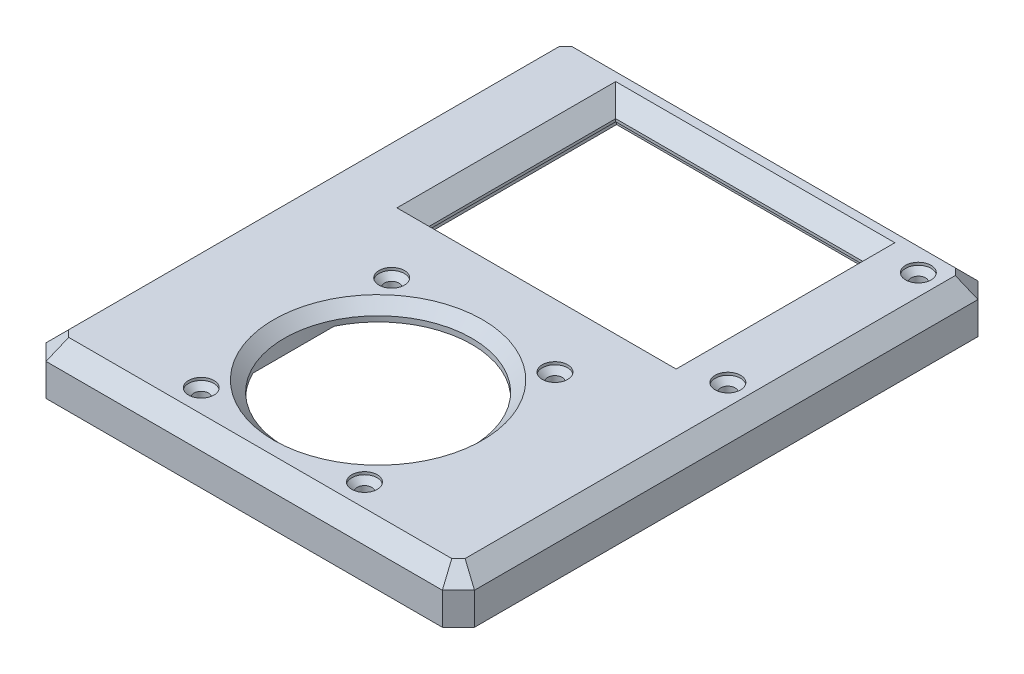
SolidWorks part; units mm, degrees
ref_plane "Front Plane" through (0, 0, 0) normal (0, 0, 1) x (1, 0, 0)
ref_plane "Top Plane" through (0, 0, 0) normal (0, 1, 0) x (1, 0, 0)
ref_plane "Right Plane" through (0, 0, 0) normal (1, 0, 0) x (0, 0, -1)
sketch "Sketch1" plane through (0, 0, 0) normal (0, 1, 0) x (1, 0, 0)
  line L1 (40, 50) -> (-40, 50)
  line L2 (40, 50) -> (40, -50)
  line L3 (40, -50) -> (-40, -50)
  line L4 (-40, 50) -> (-40, -50)
  line L5 (40, 50) -> (-40, -50) construction
  line L6 (40, -50) -> (-40, 50) construction
  point P0 (0, 0)
  dimension "D1" = 80
  dimension "D2" = 100
extrude "Main Base" add sketch "Sketch1" along normal blind 9
sketch "Sketch2" plane through (0, 0, 0) normal (0, -1, 0) x (1, 0, 0)
  circle A0 centre (0, 25) radius 17.5
  dimension "D1" = 35
  dimension "D2" = 25
extrude "ANO Main Wheel Hole" cut sketch "Sketch2" against normal through all both and the other way through all
chamfer "ANO Main Wheel Hole Chamfer" distance 2 angle 45 1 edges at (0, 9, 7.5)
sketch "Sketch3" plane through (0, 0, 0) normal (0, -1, 0) x (1, 0, 0)
  line L0 (15.24, 7.22) -> (-15.24, 42.78) construction
  circle A0 centre (-15.24, 42.78) radius 1.35
  circle A1 centre (15.24, 42.78) radius 1.35
  circle A2 centre (15.24, 7.22) radius 1.35
  circle A3 centre (-15.24, 7.22) radius 1.35
  circle A4 centre (0, 25) radius 17.5 construction
  circle A5 centre (0, 25) radius 17.5 construction
  point P16 (0, 25)
  dimension "D1" = 2.7
  dimension "D2" = 30.48
  dimension "D3" = 35.56
extrude "ANO Mount Holes Cut" cut sketch "Sketch3" against normal through all and the other way through all
sketch "ANO Board Dimensions" plane through (0, 0, 0) normal (0, -1, 0) x (1, 0, 0)
  line L0 (-17.78, 7.22) -> (-17.78, 42.78)
  line L5 (-15.24, 45.32) -> (15.24, 45.32)
  line L6 (17.78, 42.78) -> (17.78, 7.22)
  line L7 (15.24, 4.68) -> (-15.24, 4.68)
  circle A0 centre (-15.24, 42.78) radius 2.54
  circle A1 centre (-15.24, 7.22) radius 2.54
  circle A2 centre (15.24, 7.22) radius 2.54
  circle A3 centre (15.24, 42.78) radius 2.54
  arc A5 (-17.78, 7.22) -> (-15.24, 4.68) centre (-15.24, 7.22) ccw
  arc A6 (17.78, 7.22) -> (15.24, 4.68) centre (15.24, 7.22) cw
  arc A7 (15.24, 45.32) -> (17.78, 42.78) centre (15.24, 42.78) cw
  arc A8 (-17.78, 42.78) -> (-15.24, 45.32) centre (-15.24, 42.78) cw
  dimension "D2" = 35.56
  dimension "D3" = 40.64
sketch "Sketch6" plane through (0, 0, 0) normal (0, -1, 0) x (1, 0, 0)
  line L0 (-17.78, 25) -> (-17.78, 37.7)
  line L1 (-17.78, 7.22) -> (-17.78, 42.78) construction
  line L2 (-15.24, 45.32) -> (15.24, 45.32) construction
  line L3 (-10.16, 45.32) -> (10.16, 45.32)
  line L4 (0, 25) -> (-17.78, 25) construction
  line L5 (0, 25) -> (0, 45.32) construction
  line L12 (17.78, 25) -> (17.78, 37.7)
  line L13 (-17.78, 25) -> (-17.78, 12.3)
  line L15 (-10.16, 4.68) -> (10.16, 4.68)
  line L16 (17.78, 12.3) -> (17.78, 25)
  arc A0 (-17.78, 37.7) -> (-15.24, 40.24) centre (-15.24, 37.7) cw
  circle A1 centre (-15.24, 42.78) radius 2.54 construction
  arc A2 (-15.24, 40.24) -> (-12.7, 42.78) centre (-15.24, 42.78) ccw
  arc A3 (-12.7, 42.78) -> (-10.16, 45.32) centre (-10.16, 42.78) cw
  arc A13 (17.78, 37.7) -> (15.24, 40.24) centre (15.24, 37.7) ccw
  arc A14 (15.24, 40.24) -> (12.7, 42.78) centre (15.24, 42.78) cw
  arc A15 (12.7, 42.78) -> (10.16, 45.32) centre (10.16, 42.78) ccw
  arc A16 (-17.78, 12.3) -> (-15.24, 9.76) centre (-15.24, 12.3) ccw
  arc A17 (-15.24, 9.76) -> (-12.7, 7.22) centre (-15.24, 7.22) cw
  arc A18 (-12.7, 7.22) -> (-10.16, 4.68) centre (-10.16, 7.22) ccw
  arc A19 (10.16, 4.68) -> (12.7, 7.22) centre (10.16, 7.22) ccw
  arc A20 (12.7, 7.22) -> (15.24, 9.76) centre (15.24, 7.22) cw
  arc A21 (15.24, 9.76) -> (17.78, 12.3) centre (15.24, 12.3) ccw
  circle A22 centre (-15.24, 7.22) radius 1.35 construction
  circle A23 centre (15.24, 7.22) radius 1.35 construction
  point P14 (0, 25)
  point P44 (0, 0)
  point P45 (-12.7, 6.7753)
  point P46 (-10.1696, 7.0635)
  point P47 (16.3063, 9.5253)
  point P48 (0, 25)
extrude "ANO Board Offset Cut" cut sketch "Sketch6" against normal offset from surface (6 mm away) 3 up to face at (-15.24, 9, 5.87)
sketch "Sketch12" plane through (0, 0, 0) normal (0, -1, 0) x (1, 0, 0)
  line L0 (15.24, 4.68) -> (-15.24, 4.68) construction
  line L5 (17.78, 42.78) -> (17.78, 7.22) construction
  line L6 (-15.24, 45.32) -> (15.24, 45.32) construction
  line L7 (-17.78, 7.22) -> (-17.78, 42.78) construction
  line L20 (15.24, 4.68) -> (-15.24, 4.68) construction
  line L21 (17.78, 42.78) -> (17.78, 7.22) construction
  line L22 (-15.24, 45.32) -> (15.24, 45.32) construction
  line L23 (-17.78, 7.22) -> (-17.78, 42.78) construction
  line L24 (18.28, 42.78) -> (18.28, 7.22)
  line L25 (-15.24, 45.82) -> (15.24, 45.82)
  line L26 (-18.28, 7.22) -> (-18.28, 42.78)
  line L27 (15.24, 4.18) -> (-15.24, 4.18)
  arc A3 (-17.78, 42.78) -> (-15.24, 45.32) centre (-15.24, 42.78) cw construction
  arc A4 (17.78, 42.78) -> (15.24, 45.32) centre (15.24, 42.78) ccw construction
  arc A5 (-17.78, 7.22) -> (-15.24, 4.68) centre (-15.24, 7.22) ccw construction
  arc A6 (15.24, 4.68) -> (17.78, 7.22) centre (15.24, 7.22) ccw construction
  arc A7 (15.24, 4.18) -> (18.28, 7.22) centre (15.24, 7.22) ccw
  arc A8 (18.28, 42.78) -> (15.24, 45.82) centre (15.24, 42.78) ccw
  arc A9 (-18.28, 42.78) -> (-15.24, 45.82) centre (-15.24, 42.78) cw
  arc A10 (-18.28, 7.22) -> (-15.24, 4.18) centre (-15.24, 7.22) ccw
  dimension "D1" = 0.5
extrude "ANO Board Insert Cut" cut sketch "Sketch12" against normal offset from surface (4 mm away) 5 up to face at (-15.24, 9, 5.87)
chamfer "ANO Offset Chamfer" distance 2 angle 45 16 edges at (-11.9561, 6, 44.5761) (-13.4439, 6, 40.9839) (-17.0361, 6, 39.4961) (17.78, 6, 25) (11.9561, 6, 5.4239) (0, 6, 4.68) (13.4439, 6, 9.0161) (-11.9561, 6, 5.4239) (17.0361, 6, 10.5039) (-13.4439, 6, 9.0161) (-17.0361, 6, 10.5039) (17.0361, 6, 39.4961) (-17.78, 6, 25) (13.4439, 6, 40.9839) (11.9561, 6, 44.5761) (0, 6, 45.32)
chamfer "ANO Board Insert Chamfer" distance 4 angle 45 8 edges at (0, 0, 4.18) (17.3896, 0, 5.0704) (-17.3896, 0, 5.0704) (18.28, 0, 25) (-18.28, 0, 25) (17.3896, 0, 44.9296) (-17.3896, 0, 44.9296) (0, 0, 45.82)
sketch "Sketch7" plane through (0, 9, 0) normal (0, 1, 0) x (1, 0, 0)
  circle A0 centre (-15.24, -7.22) radius 2.375
  circle A1 centre (-15.24, -42.78) radius 2.375
  circle A2 centre (15.24, -42.78) radius 2.375
  circle A3 centre (15.24, -7.22) radius 2.375
  dimension "D1" = 4.75
extrude "ANO Screw Countersink Cut" cut sketch "Sketch7" against normal blind 2.5
chamfer "ANO Screw Countersink Chamfer" distance 2 angle 45 4 edges at (-15.24, 6.5, 45.155) (15.24, 6.5, 45.155) (15.24, 6.5, 9.595) (-15.24, 6.5, 9.595)
sketch "Sketch8" plane through (0, 9, 0) normal (0, 1, 0) x (1, 0, 0)
  line L1 (23.06, 42.42) -> (-23.06, 42.42)
  line L2 (23.06, 42.42) -> (23.06, 7.58)
  line L3 (23.06, 7.58) -> (-23.06, 7.58)
  line L4 (-23.06, 42.42) -> (-23.06, 7.58)
  line L5 (23.06, 42.42) -> (-23.06, 7.58) construction
  line L6 (23.06, 7.58) -> (-23.06, 42.42) construction
  point P0 (0, 25)
  dimension "D1" = 46.12
  dimension "D2" = 34.84
  dimension "D3" = 25
extrude "Display Main Cut" cut sketch "Sketch8" against normal through all
chamfer "Display Chamfer" distance 3 angle 45 4 edges at (0, 9, -7.58) (23.06, 9, -25) (0, 9, -42.42) (-23.06, 9, -25)
sketch "Sketch9" plane through (0, 0, 0) normal (0, -1, 0) x (1, 0, 0)
  line L8 (-23.06, -42.42) -> (-23.06, -7.58) construction
  line L9 (-25.52, -4.95) -> (29.68, -4.95) construction
  line L10 (-25.52, -4.95) -> (-25.52, -45.05) construction
  line L11 (-25.52, -45.05) -> (29.68, -45.05) construction
  line L12 (29.68, -4.95) -> (29.68, -45.05) construction
  line L13 (-26.02, -4.45) -> (-26.02, -45.55)
  line L14 (-26.02, -45.55) -> (30.18, -45.55)
  line L15 (30.18, -4.45) -> (30.18, -45.55)
  line L16 (-26.02, -4.45) -> (30.18, -4.45)
  point P6 (-23.06, -25)
  point P7 (-25.52, -25)
  dimension "D1" = 55.2
  dimension "D2" = 40.1
  dimension "D3" = 2.46
  dimension "D4" = 0.5
extrude "Display Offset Cut" cut sketch "Sketch9" against normal offset from surface (5.5 mm away) 3.5 up to face at (0, 9, -25)
sketch "Sketch10" plane through (0, 0, 0) normal (0, -1, 0) x (1, 0, 0)
  line L0 (-23.06, -7.58) -> (-23.06, -42.42) construction
  line L1 (-31.025, -4.875) -> (36.225, -4.875) construction
  line L2 (-31.025, -4.875) -> (-31.025, -45.125) construction
  line L3 (-31.025, -45.125) -> (36.225, -45.125) construction
  line L4 (36.225, -4.875) -> (36.225, -45.125) construction
  line L6 (-25.52, -4.95) -> (-25.52, -45.05) construction
  line L7 (33.08, -42.78) -> (-27.88, -7.22) construction
  line L8 (-27.88, -42.78) -> (33.08, -7.22) construction
  line L9 (-31.025, -25) -> (36.225, -25) construction
  circle A0 centre (-27.88, -7.22) radius 1.35 construction
  circle A1 centre (-27.88, -42.78) radius 1.35 construction
  circle A2 centre (33.08, -42.78) radius 1.35
  circle A3 centre (33.08, -7.22) radius 1.35
  point P6 (-23.06, -25)
  point P7 (-31.025, -25)
  point P18 (2.6, -25)
  point P23 (2.6, -25)
  dimension "D6" = 2.7
  dimension "D1" = 67.25
  dimension "D2" = 40.25
  dimension "D3" = 5.505
  dimension "D4" = 60.96
  dimension "D5" = 35.56
extrude "Display Mount Holes Cut" cut sketch "Sketch10" against normal through all
sketch "Sketch14" plane through (0, 0, 0) normal (0, -1, 0) x (1, 0, 0)
  circle A0 centre (-27.88, -7.22) radius 1.225
  circle A1 centre (-27.88, -42.78) radius 1.225
  dimension "D1" = 2.45
extrude "Display Secondary Mount Holes" cut sketch "Sketch14" against normal offset from surface (6 mm away) 3 up to face at (33.08, 9, -44.13)
sketch "Sketch11" plane through (0, 9, 0) normal (0, 1, 0) x (1, 0, 0)
  circle A0 centre (-27.88, 7.22) radius 2.375 construction
  circle A1 centre (-27.88, 42.78) radius 2.375 construction
  circle A2 centre (33.08, 42.78) radius 2.375
  circle A3 centre (33.08, 7.22) radius 2.375
  dimension "D1" = 4.75
extrude "Display Screw Countersink" cut sketch "Sketch11" against normal blind 2.5
chamfer "Display Screw Countersink Chamfer" distance 2 angle 45 2 edges at (33.08, 6.5, -40.405) (33.08, 6.5, -4.845)
sketch "Sketch13" plane through (0, 0, 0) normal (0, -1, 0) x (1, 0, 0)
  line L8 (36.725, -45.625) -> (36.725, -4.375)
  line L9 (-31.525, -45.625) -> (36.725, -45.625)
  line L10 (-31.525, -4.375) -> (-31.525, -45.625)
  line L11 (36.725, -4.375) -> (-31.525, -4.375)
  line L12 (36.725, -45.625) -> (36.725, -4.375)
  line L13 (-31.525, -45.625) -> (36.725, -45.625)
  line L14 (-31.525, -4.375) -> (-31.525, -45.625)
  line L15 (36.725, -4.375) -> (-31.525, -4.375)
  dimension "D1" = 0.5
extrude "Display Surface Offset Cut" cut sketch "Sketch13" against normal offset from surface (2 mm away) 7 contours L12 L15 L14 L13 up to face at (33.08, 9, -40.405)
chamfer "Display Back Chamfer" distance 2 angle 45 4 edges at (36.725, 0, -25) (2.6, 0, -45.625) (-31.525, 0, -25) (2.6, 0, -4.375)
sketch "Sketch16" plane through (0, 2, 0) normal (0, -1, 0) x (1, 0, 0)
  line L0 (30.18, -4.45) -> (30.18, -45.55) construction
  line L1 (36.725, -13.765) -> (36.725, -36.235)
  line L2 (36.725, -4.375) -> (36.725, -45.625) construction
  line L3 (30.18, -4.45) -> (30.18, -45.55) construction
  line L4 (30.18, -7.22) -> (30.18, -42.78)
  arc A0 (30.18, -7.22) -> (33.08, -10.12) centre (33.08, -7.22) ccw
  arc A1 (30.18, -42.78) -> (33.08, -39.88) centre (33.08, -42.78) cw
  arc A2 (33.08, -10.12) -> (36.725, -13.765) centre (33.08, -13.765) cw
  arc A3 (33.08, -39.88) -> (36.725, -36.235) centre (33.08, -36.235) ccw
extrude "Display Wire Spacer Cut" cut sketch "Sketch16" against normal up to surface (3.5 mm away) up to face at (2.08, 5.5, -25)
chamfer "Chamfer9" distance 3 angle 45 4 edges at (-40, 4.5, -50) (40, 4.5, -50) (-40, 4.5, 50) (40, 4.5, 50)
chamfer "Chamfer10" distance 3 angle 45 8 edges at (38.5, 9, -48.5) (40, 9, 0) (38.5, 9, 48.5) (0, 9, 50) (-38.5, 9, 48.5) (-40, 9, 0) (-38.5, 9, -48.5) (0, 9, -50)
equation "\"ButtonSurfaceOffset\"= 5"
equation "\"D1@ANO Board Insert Cut\"=\"ButtonSurfaceOffset\""
equation "\"WallThickness\"= 9"
equation "\"D1@Main Base\"=\"WallThickness\""
equation "\"D1@ANO Board Offset Cut\"=\"ButtonSpacerCut\""
equation "\"ButtonSpacerCut\"= \"ButtonSurfaceOffset\" - \"ButtonBoardSpace\""
equation "\"D1@ANO Offset Chamfer\"=\"ButtonBoardSpace\""
equation "\"D1@ANO Board Insert Chamfer\"=\"WallThickness\"-\"ButtonSurfaceOffset\""
equation "\"ButtonBoardSpace\"= 2"
equation "\"DisplaySurfaceOffset\"= 2"
equation "\"D1@Display Offset Cut\"=\"WallThickness\"-\"DisplaySurfaceOffset\"-3.5"
equation "\"D1@Display Surface Offset Cut\" = \"WallThickness\" - \"DisplaySurfaceOffset\""
equation "\"D1@Display Back Chamfer\"=\"DisplaySurfaceOffset\""
